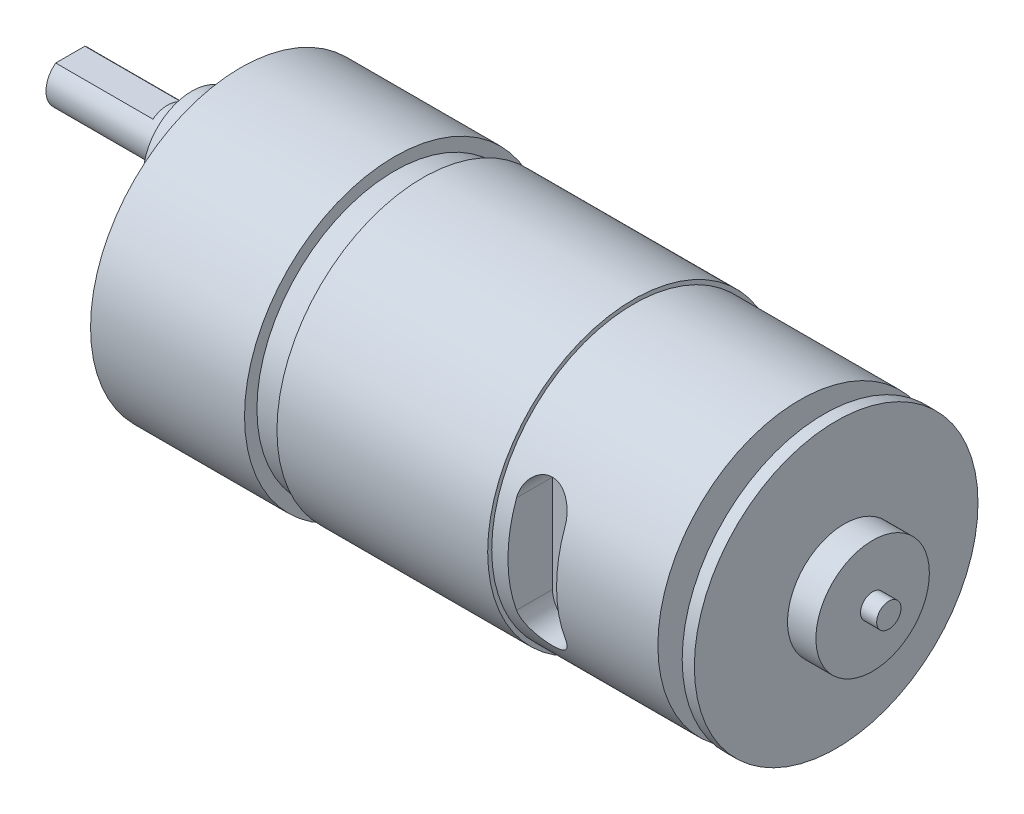
SolidWorks part; units mm, degrees
ref_plane "前视基准面" through (0, 0, 0) normal (0, 0, 1) x (1, 0, 0)
ref_plane "上视基准面" through (0, 0, 0) normal (0, 1, 0) x (1, 0, 0)
ref_plane "右视基准面" through (0, 0, 0) normal (1, 0, 0) x (0, 0, -1)
sketch "草图1" plane through (0, 0, 0) normal (0, 1, 0) x (1, 0, 0)
  line L0 (-22.9224, 0) -> (59.8409, 0) construction
  line L1 (0, 0) -> (0, 18.5)
  line L2 (0, 18.5) -> (19, 18.5)
  line L3 (19, 18.5) -> (19, 16.9707)
  line L4 (19, 16.9707) -> (22.5, 16.9707)
  line L5 (22.5, 16.9707) -> (22.5, 18)
  line L6 (22.5, 18) -> (48.5, 18)
  line L7 (48.5, 18) -> (48.5, 17.5)
  line L8 (48.5, 17.5) -> (69, 17.5)
  line L9 (69, 17.5) -> (69, 0)
  line L10 (69, 0) -> (0, 0)
  dimension "D1" = 37
  dimension "D2" = 19
  dimension "D3" = 3.5
  dimension "D4" = 50
  dimension "D5" = 26
  dimension "D6" = 35
  dimension "D7" = 36
revolve "旋转1" add sketch "草图1" angle 360 about L0
sketch "草图2" plane through (0, 0, 0) normal (-1, 0, 0) x (0, 0, 1)
  arc A0 (-8.9443, 8) -> (8.9443, 8) centre (0, 0) ccw
  arc A1 (-8.9443, 8) -> (8.9443, 8) centre (0, 7) ccw
  dimension "D1" = 7
  dimension "D2" = 18
  dimension "D3" = 12
extrude "切除-拉伸1" cut sketch "草图2" against normal blind 1
sketch "草图3" plane through (0, 0, 0) normal (-1, 0, 0) x (0, 0, 1)
  circle A0 centre (0, 7) radius 6
extrude "凸台-拉伸1" add sketch "草图3" along normal blind 6
sketch "草图4" plane through (-6, 0, 0) normal (-1, 0, 0) x (0, 0, 1)
  circle A0 centre (0, 7) radius 3
extrude "凸台-拉伸2" add sketch "草图4" along normal blind 15
sketch "草图5" plane through (-21, 0, 0) normal (-1, 0, 0) x (0, 0, 1)
  line L1 (-3.9258, 11.2187) -> (4.5061, 11.2187)
  line L2 (-3.9258, 11.2187) -> (-3.9258, 9.4)
  line L3 (-3.9258, 9.4) -> (4.5061, 9.4)
  line L4 (4.5061, 11.2187) -> (4.5061, 9.4)
  circle A0 centre (0, 7) radius 3 construction
  dimension "D1" = 2.4
extrude "切除-拉伸2" cut sketch "草图5" against normal blind 12
sketch "草图6" plane through (0, 0, 0) normal (-1, 0, 0) x (0, 0, 1)
  circle A0 centre (0, 0) radius 15.5 construction
  circle A1 centre (-15.5, 0) radius 1.5
  circle A2 centre (-7.75, 13.4234) radius 1.5
  circle A3 centre (7.75, 13.4234) radius 1.5
  circle A4 centre (15.5, 0) radius 1.5
  circle A5 centre (7.75, -13.4234) radius 1.5
  circle A6 centre (-7.75, -13.4234) radius 1.5
  circle A7 centre (-13.4234, 7.75) radius 1.5
  point P17 (0, 0)
  point P20 (0, 0)
  dimension "D1" = 6
  dimension "D3" = 3
  dimension "D2" = 2
extrude "切除-拉伸3" cut sketch "草图6" against normal blind 5
sketch "草图8" plane through (0, 0, 0) normal (-1, 0, 0) x (0, 0, 1)
  circle A0 centre (-13.4234, 7.75) radius 2
  circle A1 centre (13.4234, 7.75) radius 2
  circle A2 centre (0, -15.5) radius 2
  point P9 (0, 0)
  dimension "D1" = 3
extrude "切除-拉伸4" cut sketch "草图8" against normal blind 5
sketch "草图9" plane through (0, 0, 0) normal (0, 0, 1) x (1, 0, 0)
  line L0 (48.5, -17.5) -> (48.5, 17.5) construction
  line L2 (50.5, -6) -> (50.5, 6)
  line L4 (56.5, -6) -> (56.5, 6)
  line L5 (50.5, -6) -> (56.5, 6) construction
  line L6 (50.5, 6) -> (56.5, -6) construction
  arc A0 (50.5, 6) -> (56.5, 6) centre (53.5, 6) cw
  arc A1 (50.5, -6) -> (56.5, -6) centre (53.5, -6) ccw
  point P0 (53.5, 0)
  dimension "D1" = 12
  dimension "D2" = 0
  dimension "D3" = 6
  dimension "D4" = 2
extrude "切除-拉伸5" cut sketch "草图9" against normal through all and the other way through all
sketch "草图10" plane through (0, 0, 0) normal (0, 0, 1) x (1, 0, 0)
  line L2 (50.5, 6) -> (50.5, -6)
  line L3 (56.5, -6) -> (56.5, 6)
  line L4 (50.5, 6) -> (50.5, -6)
  line L5 (56.5, -6) -> (56.5, 6)
  arc A2 (56.5, 6) -> (50.5, 6) centre (53.5, 6) ccw
  arc A3 (50.5, -6) -> (56.5, -6) centre (53.5, -6) ccw
  arc A4 (56.5, 6) -> (50.5, 6) centre (53.5, 6) ccw
  arc A5 (50.5, -6) -> (56.5, -6) centre (53.5, -6) ccw
  dimension "D1" = 0
extrude "凸台-拉伸3" add sketch "草图10" along normal blind 12 and the other way blind 12
sketch "草图11" plane through (69, 0, 0) normal (1, 0, 0) x (0, 0, -1)
  circle A0 centre (0, 0) radius 4.5
extrude "凸台-拉伸4" add sketch "草图11" along normal blind 3
sketch "草图12" plane through (72, 0, 0) normal (1, 0, 0) x (0, 0, -1)
  circle A0 centre (0, 0) radius 17.5
extrude "凸台-拉伸5" add sketch "草图12" along normal blind 1.5
sketch "草图13" plane through (73.5, 0, 0) normal (1, 0, 0) x (0, 0, -1)
  line L0 (0, 9.64) -> (0, -9.3869) construction
  line L1 (-12.9691, 2) -> (-12.7691, 2)
  line L2 (-12.9691, 2) -> (-12.9691, -2)
  line L3 (-12.9691, -2) -> (-12.7691, -2)
  line L4 (-12.7691, 2) -> (-12.7691, -2)
  line L5 (-12.9691, 2) -> (-12.7691, -2) construction
  line L6 (-12.9691, -2) -> (-12.7691, 2) construction
  line L7 (12.9691, -2) -> (12.7691, 2) construction
  line L8 (12.9691, 2) -> (12.7691, -2) construction
  line L9 (12.7691, 2) -> (12.7691, -2)
  line L10 (12.9691, -2) -> (12.7691, -2)
  line L11 (12.9691, 2) -> (12.9691, -2)
  line L12 (12.9691, 2) -> (12.7691, 2)
  point P0 (-12.8691, 0)
  point P12 (12.8691, 0)
  dimension "D1" = 0.2
  dimension "D2" = 4
  dimension "D3" = 0
extrude "凸台-拉伸6" add sketch "草图13" against normal blind 5
sketch "草图14" plane through (73.5, 0, 0) normal (1, 0, 0) x (0, 0, -1)
  circle A0 centre (0, 0) radius 1.5
extrude "凸台-拉伸7" add sketch "草图14" along normal blind 1
sketch "草图15" plane through (74.5, 0, 0) normal (1, 0, 0) x (0, 0, -1)
  circle A0 centre (0, 0) radius 7
extrude "凸台-拉伸8" add sketch "草图15" along normal blind 3.5
sketch "草图16" plane through (78, 0, 0) normal (1, 0, 0) x (0, 0, -1)
  circle A0 centre (0, 0) radius 1.5
extrude "凸台-拉伸9" add sketch "草图16" along normal blind 2
